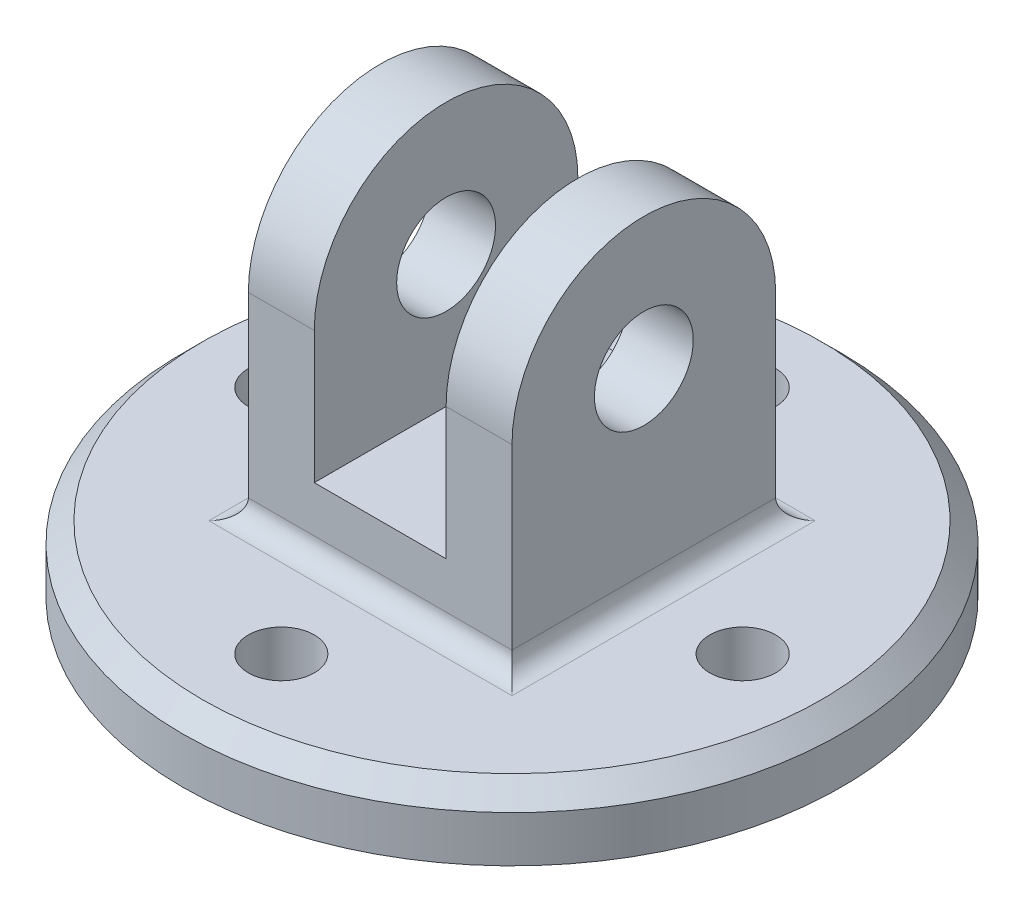
SolidWorks part; units mm, degrees
material "AISI 316 Annealed Stainless Steel Bar (SS)"
ref_plane "Front Plane" through (0, 0, 0) normal (0, 0, 1) x (1, 0, 0)
ref_plane "Top Plane" through (0, 0, 0) normal (0, 1, 0) x (1, 0, 0)
ref_plane "Right Plane" through (0, 0, 0) normal (1, 0, 0) x (0, 0, -1)
sketch "Sketch1" plane through (0, 0, 0) normal (0, 1, 0) x (1, 0, 0)
  circle A0 centre (0, 0) radius 63.5
  dimension "D1" = 127
extrude "Base" add sketch "Sketch1" along normal blind 12.7
sketch "Sketch2" plane through (0, 0, 0) normal (0, 0, 1) x (1, 0, 0)
  line L0 (0, 0) -> (0, 53.0447) construction
  line L1 (-12.7, 25.4) -> (12.7, 25.4)
  line L2 (12.7, 25.4) -> (12.7, 76.2)
  line L3 (12.7, 76.2) -> (25.4, 76.2)
  line L4 (25.4, 76.2) -> (25.4, 12.7)
  line L5 (63.5, 12.7) -> (-63.5, 12.7) construction
  line L6 (25.4, 12.7) -> (-25.4, 12.7)
  line L7 (-25.4, 76.2) -> (-25.4, 12.7)
  line L8 (-12.7, 76.2) -> (-25.4, 76.2)
  line L9 (-12.7, 25.4) -> (-12.7, 76.2)
  point P12 (0, 12.7)
  point P15 (0, 25.4)
  dimension "D1" = 12.7
  dimension "D2" = 12.7
  dimension "D3" = 25.4
  dimension "D4" = 50.8
extrude "Mount" add sketch "Sketch2" along normal mid plane 50.8
fillet "Fillet1" 2 edges at (19.05, 76.2, 25.4) (19.05, 76.2, -25.4) type full round first side face at (0, 47.625, 25.4) second side face at (0, 47.625, -25.4) middle face at (19.05, 76.2, 0)
fillet "Fillet2" 2 edges at (-19.05, 76.2, 25.4) (-19.05, 76.2, -25.4) type full round first side face at (0, 41.275, 25.4) second side face at (0, 41.275, -25.4) middle face at (-19.05, 76.2, 0)
sketch "Sketch3" plane through (0, 0, 0) normal (1, 0, 0) x (0, 0, -1)
  line L0 (0, 0) -> (0, 50.8) construction
  line L1 (-25.4, 25.4) -> (25.4, 25.4) construction
  circle A0 centre (0, 50.8) radius 9.525
  dimension "D1" = 19.05
  dimension "D2" = 25.4
extrude "Pin Hole" cut sketch "Sketch3" against normal through all both and the other way through all
sketch "Sketch4" plane through (0, 12.7, 0) normal (0, 1, 0) x (1, 0, 0)
  circle A0 centre (0, 0) radius 44.45 construction
  circle A1 centre (0, -44.45) radius 6.35
  circle A2 centre (-44.45, 0) radius 6.35
  circle A3 centre (0, 44.45) radius 6.35
  circle A4 centre (44.45, 0) radius 6.35
  point P14 (0, 0)
  dimension "D1" = 88.9
  dimension "D2" = 12.7
  dimension "D3" = 4
extrude "Bolt Pattern" cut sketch "Sketch4" against normal through all
fillet "Fillet3" radius 3.81 4 edges at (0, 12.7, -25.4) (-25.4, 12.7, 0) (25.4, 12.7, 0) (0, 12.7, 25.4)
chamfer "Chamfer1" distance 3.81 angle 45 1 edges at (0, 12.7, 63.5)
